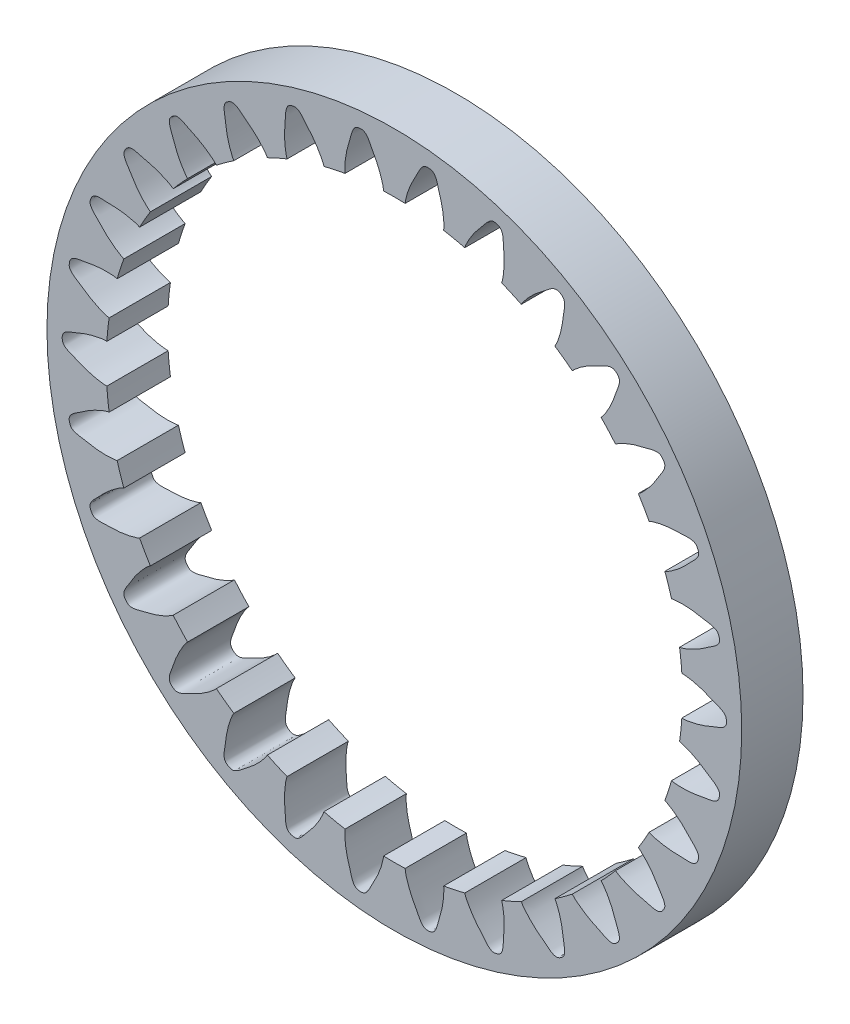
SolidWorks part; units mm, degrees
ref_plane "Front" through (0, 0, 0) normal (0, 0, 1) x (1, 0, 0)
ref_plane "Top" through (0, 0, 0) normal (0, 1, 0) x (1, 0, 0)
ref_plane "Right" through (0, 0, 0) normal (1, 0, 0) x (0, 0, -1)
ref_axis "Axis1" through (0, 0, 50) along (0, 0, -1)
sketch "SketchRevolveRing_Gear_Fixed01" plane through (0, 0, 0) normal (1, 0, 0) x (0, 0, -1)
  line L0 (0, 0) -> (1, 0) construction
  line L1 (-1.5, 14.1) -> (-1.5, 17)
  line L2 (-1.5, 17) -> (1.5, 17)
  line L3 (1.5, 17) -> (1.5, 14.1)
  line L4 (1.5, 14.1) -> (-1.5, 14.1)
  dimension "Side1" = 1.5
  dimension "OutsideRadius" = 17
  dimension "Side2" = 1.5
  dimension "MinorDiameter" = 14.1
revolve "Ring_Gear_Fixed01" add sketch "SketchRevolveRing_Gear_Fixed01" angle 360 about L0
sketch "SketchToothRing_Gear_Fixed01" plane through (0, 0, 0) normal (0, 0, 1) x (1, 0, 0)
  arc A0 (14.0635, -0.9474) -> (14.0635, 0.9474) centre (0, 0) ccw
  spline S0 degree 3 poles (14.0635, 0.9474) (14.1276, 0.9504) (14.3059, 0.9378) (14.6504, 0.8806) (15.1483, 0.7462) (15.6463, 0.5223) (16.0477, 0.3793) (16.2263, 0.2044) (16.2565, 0.0458) (16.2564, -0.1005) (16.211, -0.2108) (16.0697, -0.3789) (15.6533, -0.5141) (15.1494, -0.7482) (14.5883, -0.8934) (14.2416, -0.9557) (14.0635, -0.9474) knots 0 0 0 0 0.038206 0.106129 0.208012 0.343856 0.432946 0.457131 0.488937 0.526745 0.542869 0.558992 0.656144 0.791988 0.893871 1 1 1 1
extrude "ToothExtrudeCutRing_Gear_Fixed01" cut sketch "SketchToothRing_Gear_Fixed01" against normal blind 2.5 and the other way blind 2.5
pattern_circular "PatternRing_Gear_Fixed01" count 30 every 12 about axis through (0, 0, 50) along (0, 0, -1) of "ToothExtrudeCutRing_Gear_Fixed01"
sketch "AuxiliarySketchRing_Gear_Fixed01" plane through (0, 0, 0) normal (0, 0, 1) x (1, 0, 0)
  circle A0 centre (0, 0) radius 15 construction
  circle A1 centre (0, 0) radius 14.0954 construction
  circle A2 centre (0, 0) radius 16.25 construction
  circle A3 centre (0, 0) radius 14 construction
  dimension "PitchDiameter" = 30
  dimension "BaseDiameter" = 28.1908
  dimension "MajorDiameter" = 32.5
  dimension "MinorDiameter" = 28
